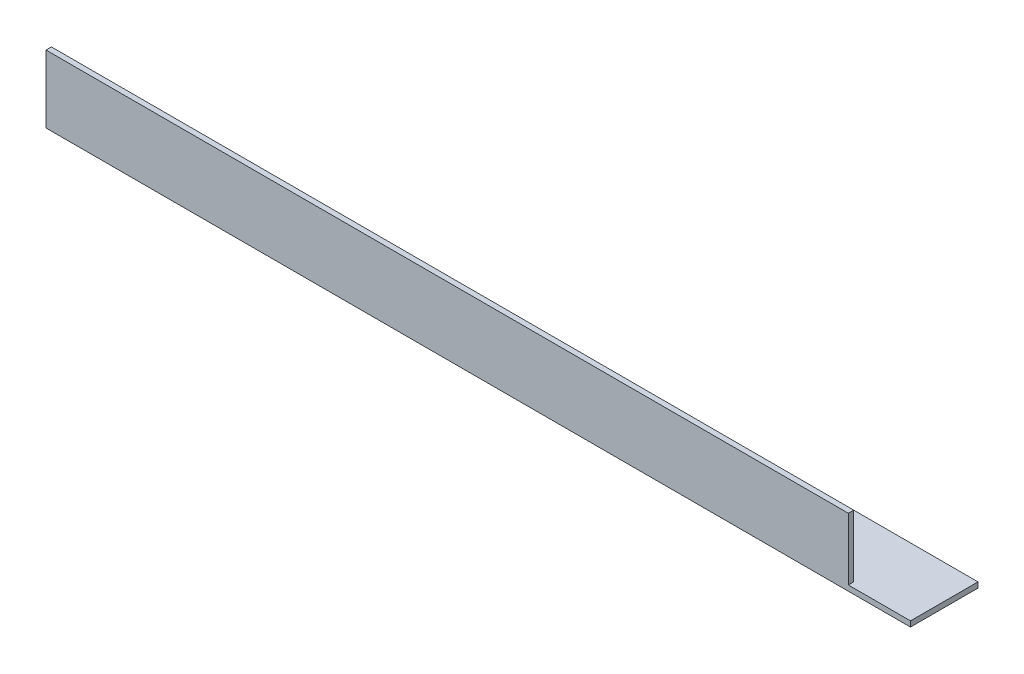
SolidWorks part; units mm, degrees
ref_plane "Спереди" through (0, 0, 0) normal (0, 0, 1) x (1, 0, 0)
ref_plane "Сверху" through (0, 0, 0) normal (0, 1, 0) x (1, 0, 0)
ref_plane "Справа" through (0, 0, 0) normal (1, 0, 0) x (0, 0, -1)
sketch "Эскиз1" plane through (0, 0, 0) normal (1, 0, 0) x (0, 0, -1)
  line L0 (0, 25) -> (0, 0)
  line L1 (0, 0) -> (25, 0)
extrude "Вытянуть-Тонкостенный1" add sketch "Эскиз1" along normal blind 320 thin thin type one direction reverse wall 2
sketch "Эскиз3" plane through (0, 0, 0) normal (0, 0, 1) x (1, 0, 0)
  line L1 (297, 2) -> (320, 2)
  line L2 (297, 2) -> (297, 25)
  line L3 (297, 25) -> (320, 25)
  line L4 (320, 2) -> (320, 25)
  dimension "D1" = 23
extrude "Вырез-Вытянуть1" cut sketch "Эскиз3" against normal through all
